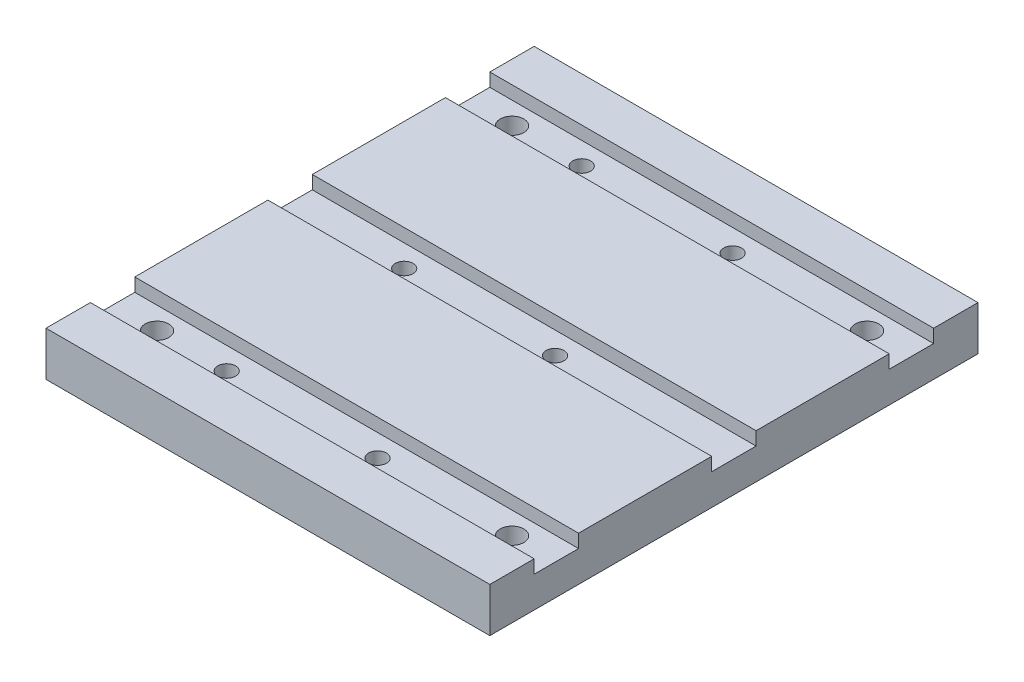
SolidWorks part; units mm, degrees
material "Acrylic (Medium-high impact)"
ref_plane "Front Plane" through (0, 0, 0) normal (0, 0, 1) x (1, 0, 0)
ref_plane "Top Plane" through (0, 0, 0) normal (0, 1, 0) x (1, 0, 0)
ref_plane "Right Plane" through (0, 0, 0) normal (1, 0, 0) x (0, 0, -1)
sketch "Sketch2" plane through (0, 0, 0) normal (0, 1, 0) x (1, 0, 0)
  line L1 (-63.5, 69.85) -> (63.5, 69.85)
  line L2 (-63.5, 69.85) -> (-63.5, -69.85)
  line L3 (-63.5, -69.85) -> (63.5, -69.85)
  line L4 (63.5, 69.85) -> (63.5, -69.85)
  line L5 (-63.5, 69.85) -> (63.5, -69.85) construction
  line L6 (-63.5, -69.85) -> (63.5, 69.85) construction
  point P0 (0, 0)
  dimension "D1" = 127
  dimension "D2" = 139.7
extrude "Boss-Extrude1" add sketch "Sketch2" along normal blind 12.7
sketch "Sketch4" plane through (63.5, 0, 0) normal (1, 0, 0) x (0, 0, -1)
  line L0 (-69.85, 12.7) -> (69.85, 12.7) construction
  line L1 (-57.15, 12.7) -> (-44.45, 12.7)
  line L2 (-57.15, 12.7) -> (-57.15, 8.89)
  line L3 (-57.15, 8.89) -> (-44.45, 8.89)
  line L4 (-44.45, 12.7) -> (-44.45, 8.89)
  line L5 (-69.85, 12.7) -> (-69.85, 0) construction
  dimension "D1" = 3.81
  dimension "D2" = 12.7
  dimension "D3" = 12.7
extrude "Cut-Extrude1" cut sketch "Sketch4" against normal blind 76.2
mirror "Mirror1" about plane through (0, 0, 0) normal (0, 0, 1) of "Cut-Extrude1"
sketch "Sketch5" plane through (63.5, 0, 0) normal (1, 0, 0) x (0, 0, -1)
  line L0 (-44.45, 12.7) -> (44.45, 12.7) construction
  line L1 (-6.35, 12.7) -> (6.35, 12.7)
  line L2 (-6.35, 12.7) -> (-6.35, 8.89)
  line L3 (-6.35, 8.89) -> (6.35, 8.89)
  line L4 (6.35, 12.7) -> (6.35, 8.89)
  point P6 (0, 8.89)
  dimension "D1" = 3.81
  dimension "D2" = 12.7
extrude "Cut-Extrude2" cut sketch "Sketch5" against normal blind 76.2
mirror "Mirror3" about plane through (0, 0, 0) normal (1, 0, 0) of "Cut-Extrude2", "Mirror1", "Cut-Extrude1"
sketch "Sketch6" plane through (0, 0, 0) normal (0, -1, 0) x (1, 0, 0)
  line L0 (0, 69.85) -> (0, -69.85) construction
  line L1 (-50.8, -50.8) -> (50.8, -50.8)
  line L2 (-50.8, -50.8) -> (-50.8, 50.8)
  line L3 (-50.8, 50.8) -> (50.8, 50.8)
  line L4 (50.8, -50.8) -> (50.8, 50.8)
  line L5 (-50.8, -50.8) -> (50.8, 50.8) construction
  line L6 (-50.8, 50.8) -> (50.8, -50.8) construction
  line L7 (-63.5, 69.85) -> (63.5, 69.85) construction
  line L8 (63.5, -69.85) -> (-63.5, -69.85) construction
  point P0 (0, 0)
  dimension "D1" = 101.6
  dimension "D2" = 101.6
hole_wizard "1/4 Clearance Hole1" positions "Sketch11" profile "Sketch12" hole size "1/4" standard "ANSI Inch" end condition through all
sketch "Sketch11" plane through (0, 0, 0) normal (0, -1, 0) x (-1, 0, 0)
  point P0 (-50.8, -50.8)
  point P3 (-50.8, 50.8)
  point P6 (50.8, 50.8)
  point P9 (50.8, -50.8)
sketch "Sketch12" plane through (50.8, 0, 50.8) normal (1, 0, 0) x (0, 0, -1)
  line L0 (0, 0) -> (0, 12.7)
  line L1 (0, 12.7) -> (3.3782, 12.7)
  line L2 (3.3782, 12.7) -> (3.3782, 0)
  line L5 (3.3782, 0) -> (0, 0)
  line L11 (0, -6.35) -> (0, 107.95) construction
  dimension "Thru Hole Dia." = 6.7564
  dimension "Thru Hole Depth" = 12.7
hole_wizard "CBORE for #10 Socket Head Cap Screw1" positions "Sketch13" profile "Sketch14" counterbore size "#10" standard "ANSI Inch" end condition through all
sketch "Sketch13" plane through (0, 0, 0) normal (0, -1, 0) x (-1, 0, 0)
  line L0 (63.5, 69.85) -> (63.5, -69.85) construction
  line L1 (63.5, -69.85) -> (-63.5, -69.85) construction
  point P0 (30.8508, -50.8)
  point P3 (0, 0)
  dimension "D1" = 32.6492
  dimension "D2" = 19.05
sketch "Sketch14" plane through (-30.8508, 0, 50.8) normal (1, 0, 0) x (0, 0, -1)
  line L0 (0, 0) -> (0, 12.7)
  line L1 (0, 12.7) -> (2.5527, 12.7)
  line L3 (2.5527, 12.7) -> (2.5527, 4.826)
  line L4 (2.5527, 4.826) -> (4.7625, 4.826)
  line L5 (4.7625, 4.826) -> (4.7625, 0)
  line L7 (4.7625, 0) -> (0, 0)
  line L11 (0, -6.35) -> (0, 107.95) construction
  dimension "Thru Hole Dia." = 5.1054
  dimension "Thru Hole Depth" = 12.7
  dimension "C'Bore Dia." = 9.525
  dimension "C'Bore Depth" = 4.826
hole_wizard "CBORE for #10 Socket Head Cap Screw2" positions "Sketch15" profile "Sketch16" counterbore size "#10" standard "ANSI Inch" end condition through all
sketch "Sketch15" plane through (0, 0, 0) normal (0, -1, 0) x (-1, 0, 0)
  line L1 (63.5, 69.85) -> (63.5, -69.85) construction
  line L2 (-63.5, 69.85) -> (63.5, 69.85) construction
  point P0 (30.8508, 0)
  point P7 (0, 0)
  dimension "D1" = 32.6492
  dimension "D2" = 69.85
sketch "Sketch16" plane through (-30.8508, 0, 0) normal (1, 0, 0) x (0, 0, -1)
  line L0 (0, 0) -> (0, 12.7)
  line L1 (0, 12.7) -> (2.5527, 12.7)
  line L3 (2.5527, 12.7) -> (2.5527, 4.826)
  line L4 (2.5527, 4.826) -> (4.7625, 4.826)
  line L5 (4.7625, 4.826) -> (4.7625, 0)
  line L7 (4.7625, 0) -> (0, 0)
  line L11 (0, -6.35) -> (0, 107.95) construction
  dimension "Thru Hole Dia." = 5.1054
  dimension "Thru Hole Depth" = 12.7
  dimension "C'Bore Dia." = 9.525
  dimension "C'Bore Depth" = 4.826
mirror "Mirror4" about plane through (0, 0, 0) normal (0, 0, 1) of "CBORE for #10 Socket Head Cap Screw1"
hole_wizard "CBORE for #10 Socket Head Cap Screw3" positions "Sketch19" profile "Sketch20" counterbore size "#10" standard "ANSI Inch" end condition through all
sketch "Sketch19" plane through (0, 0, 0) normal (0, -1, 0) x (-1, 0, 0)
  line L0 (63.5, -69.85) -> (-63.5, -69.85) construction
  line L1 (-63.5, 69.85) -> (63.5, 69.85) construction
  circle A0 centre (30.8508, -50.8) radius 2.5527 construction
  circle A3 centre (30.8508, 0) radius 2.5527 construction
  point P0 (-12.3292, -50.8)
  point P2 (-12.3292, 0)
  point P9 (0, 0)
  point P12 (0, 0)
  dimension "D1" = 43.18
  dimension "D2" = 19.05
  dimension "D3" = 69.85
  dimension "D4" = 43.18
sketch "Sketch20" plane through (12.3292, 0, 50.8) normal (1, 0, 0) x (0, 0, -1)
  line L0 (0, 0) -> (0, 12.7)
  line L1 (0, 12.7) -> (2.5527, 12.7)
  line L3 (2.5527, 12.7) -> (2.5527, 4.826)
  line L4 (2.5527, 4.826) -> (4.7625, 4.826)
  line L5 (4.7625, 4.826) -> (4.7625, 0)
  line L7 (4.7625, 0) -> (0, 0)
  line L11 (0, -6.35) -> (0, 107.95) construction
  dimension "Thru Hole Dia." = 5.1054
  dimension "Thru Hole Depth" = 12.7
  dimension "C'Bore Dia." = 9.525
  dimension "C'Bore Depth" = 4.826
hole_wizard "CBORE for #10 Socket Head Cap Screw4" positions "Sketch21" profile "Sketch22" counterbore size "#10" standard "ANSI Inch" end condition through all
sketch "Sketch21" plane through (0, 0, 0) normal (0, -1, 0) x (-1, 0, 0)
  line L0 (-63.5, 69.85) -> (63.5, 69.85) construction
  circle A0 centre (30.8508, 50.8) radius 2.5527 construction
  point P0 (-12.3292, 50.8)
  dimension "D1" = 19.05
  dimension "D2" = 43.18
sketch "Sketch22" plane through (12.3292, 0, -50.8) normal (1, 0, 0) x (0, 0, -1)
  line L0 (0, 0) -> (0, 12.7)
  line L1 (0, 12.7) -> (2.5527, 12.7)
  line L3 (2.5527, 12.7) -> (2.5527, 4.826)
  line L4 (2.5527, 4.826) -> (4.7625, 4.826)
  line L5 (4.7625, 4.826) -> (4.7625, 0)
  line L7 (4.7625, 0) -> (0, 0)
  line L11 (0, -6.35) -> (0, 107.95) construction
  dimension "Thru Hole Dia." = 5.1054
  dimension "Thru Hole Depth" = 12.7
  dimension "C'Bore Dia." = 9.525
  dimension "C'Bore Depth" = 4.826
